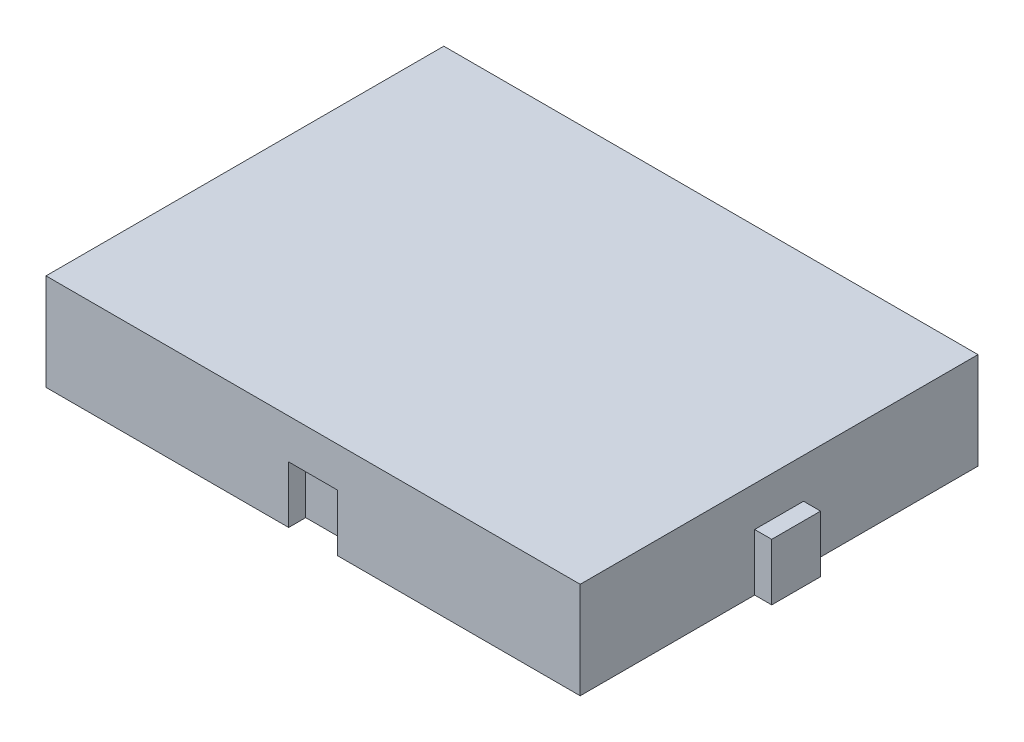
SolidWorks part; units mm, degrees
ref_plane "Front Plane" through (0, 0, 0) normal (0, 0, 1) x (1, 0, 0)
ref_plane "Top Plane" through (0, 0, 0) normal (0, 1, 0) x (1, 0, 0)
ref_plane "Right Plane" through (0, 0, 0) normal (1, 0, 0) x (0, 0, -1)
sketch "Sketch1" plane through (0, 0, 0) normal (0, 1, 0) x (1, 0, 0)
  line L1 (-23.5, -17.5) -> (23.5, -17.5)
  line L2 (-23.5, -17.5) -> (-23.5, 17.5)
  line L3 (-23.5, 17.5) -> (23.5, 17.5)
  line L4 (23.5, -17.5) -> (23.5, 17.5)
  line L5 (-23.5, -17.5) -> (23.5, 17.5) construction
  line L6 (-23.5, 17.5) -> (23.5, -17.5) construction
  point P0 (0, 0)
  dimension "D1" = 47
  dimension "D2" = 35
extrude "Boss-Extrude1" add sketch "Sketch1" along normal blind 8.5
sketch "Sketch2" plane through (0, 0, 0) normal (0, -1, 0) x (-1, 0, 0)
  line L0 (23.5, -17.5) -> (-23.5, -17.5) construction
  line L1 (2.15, 19) -> (-2.15, 19)
  line L2 (2.15, 19) -> (2.15, 17.5)
  line L3 (2.15, 17.5) -> (-2.15, 17.5)
  line L4 (-2.15, 19) -> (-2.15, 17.5)
  line L5 (-23.5, -17.5) -> (-23.5, 17.5) construction
  line L6 (-23.5, -2.15) -> (-25, -2.15)
  line L7 (-23.5, -2.15) -> (-23.5, 2.15)
  line L8 (-23.5, 2.15) -> (-25, 2.15)
  line L9 (-25, -2.15) -> (-25, 2.15)
  line L11 (-23.5, 17.5) -> (23.5, 17.5) construction
  point P12 (0, -17.5)
  point P13 (0, 17.5)
  point P14 (-25, 0)
  point P15 (0, 0)
  point P17 (0, 0)
  dimension "D1" = 4.3
  dimension "D2" = 1.5
extrude "Boss-Extrude2" add sketch "Sketch2" against normal blind 5
sketch "Sketch3" plane through (0, 0, 0) normal (0, -1, 0) x (-1, 0, 0)
  line L1 (-2.15, -16) -> (2.15, -16)
  line L2 (-2.15, -16) -> (-2.15, -17.5)
  line L3 (-2.15, -17.5) -> (2.15, -17.5)
  line L4 (2.15, -16) -> (2.15, -17.5)
  line L5 (23.5, 17.5) -> (23.5, -17.5) construction
  line L6 (23.5, -2.15) -> (22, -2.15)
  line L7 (23.5, -2.15) -> (23.5, 2.15)
  line L8 (23.5, 2.15) -> (22, 2.15)
  line L9 (22, -2.15) -> (22, 2.15)
  line L10 (23.5, -17.5) -> (-23.5, -17.5) construction
  point P4 (0, 0)
  point P12 (23.5, 0)
  point P13 (23.5, 0)
  point P14 (0, -17.5)
  point P17 (0, 0)
  point P18 (0, 0)
  dimension "D1" = 4.3
  dimension "D2" = 1.5
extrude "Cut-Extrude1" cut sketch "Sketch3" against normal blind 5
